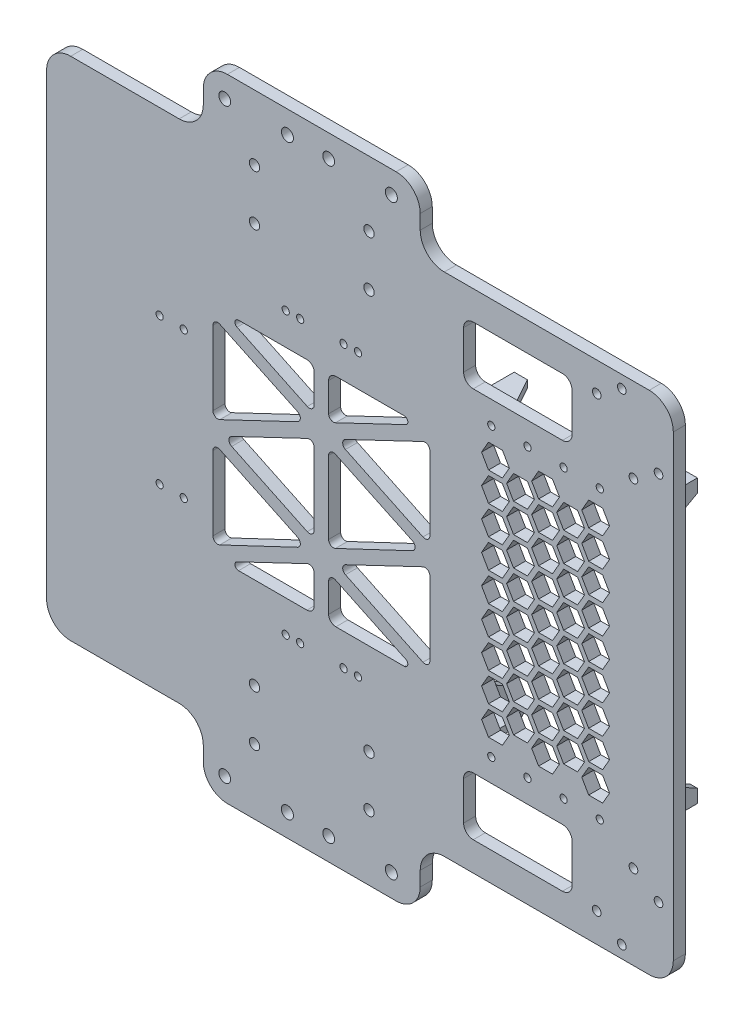
SolidWorks part; units mm, degrees
ref_plane "前视基准面" through (0, 0, 0) normal (0, 0, 1) x (1, 0, 0)
ref_plane "上视基准面" through (0, 0, 0) normal (0, 1, 0) x (1, 0, 0)
ref_plane "右视基准面" through (0, 0, 0) normal (1, 0, 0) x (0, 0, -1)
sketch "草图1" plane through (0, 0, 0) normal (0, 0, 1) x (1, 0, 0)
  line L2 (-130, 95) -> (-130, -95)
  line L3 (-120, -105) -> (-75, -105)
  line L4 (130, 95) -> (130, -95)
  line L5 (126.7518, 102.3765) -> (130, 105) construction
  line L6 (-130, -105) -> (-126.7518, -102.3765) construction
  line L9 (-65, -115) -> (-65, -121)
  line L10 (-55, -131) -> (15, -131)
  line L11 (25, -121) -> (25, -115)
  line L13 (35, -105) -> (120, -105)
  line L14 (126.7518, -102.3765) -> (130, -105) construction
  line L15 (-130, 105) -> (-126.7518, 102.3765) construction
  line L16 (-130, 0) -> (130, 0) construction
  line L17 (35, 105) -> (120, 105)
  line L18 (25, 121) -> (25, 115)
  line L19 (-55, 131) -> (15, 131)
  line L20 (-65, 115) -> (-65, 121)
  line L21 (-120, 105) -> (-75, 105)
  arc A1 (-120, -105) -> (-130, -95) centre (-120, -95) cw
  arc A3 (120, -105) -> (130, -95) centre (120, -95) ccw
  arc A8 (-65, -115) -> (-75, -105) centre (-75, -115) ccw
  arc A9 (25, -115) -> (35, -105) centre (35, -115) cw
  arc A10 (-55, -131) -> (-65, -121) centre (-55, -121) cw
  arc A11 (15, -131) -> (25, -121) centre (15, -121) ccw
  arc A12 (15, 131) -> (25, 121) centre (15, 121) cw
  arc A13 (-55, 131) -> (-65, 121) centre (-55, 121) ccw
  arc A14 (25, 115) -> (35, 105) centre (35, 115) ccw
  arc A15 (-65, 115) -> (-75, 105) centre (-75, 115) cw
  arc A16 (120, 105) -> (130, 95) centre (120, 95) cw
  arc A17 (-120, 105) -> (-130, 95) centre (-120, 95) ccw
  point P0 (0, 0)
  point P40 (25, -105)
  point P45 (25, 105)
  dimension "D2" = 10
  dimension "D3" = 65
  dimension "D4" = 10
  dimension "D5" = 105
  dimension "D7" = 10
  dimension "D8" = 10
  dimension "D10" = 10
  dimension "D12" = 10
  dimension "D13" = 105
  dimension "D18" = 90
  dimension "D19" = 6
extrude "凸台-拉伸1" add sketch "草图1" along normal blind 5
sketch "草图4" plane through (0, 0, 0) normal (0, 0, -1) x (-1, 0, 0)
  line L0 (-39, -47.5) -> (-39, -58.5)
  line L1 (-39, -58.5) -> (-50, -58.5)
  line L2 (-50, -58.5) -> (-50, -55.5)
  line L3 (-50, -55.5) -> (-42, -55.5)
  line L4 (-42, -55.5) -> (-42, -47.5)
  line L5 (-42, -47.5) -> (-39, -47.5)
  line L6 (-130, 0) -> (-25.5592, 0) construction
  line L7 (-130, -95) -> (-130, 95) construction
  line L10 (-130, -95) -> (-130, 95) construction
  dimension "D1" = 11
  dimension "D2" = 11
  dimension "D3" = 3
  dimension "D4" = 3
  dimension "D5" = 80
  dimension "D7" = 55.5
extrude "凸台-拉伸2" add sketch "草图4" along normal blind 20
sketch "草图5" plane through (0, -58.5, 0) normal (0, -1, 0) x (1, 0, 0)
  line L0 (50, -10) -> (44.5, -20)
  line L1 (50, -20) -> (50, 0) construction
  line L2 (50, -20) -> (39, -20) construction
  line L3 (44.5, -20) -> (50, -20)
  line L4 (50, -20) -> (50, -10)
  dimension "D1" = 10
  dimension "D2" = 5.5
extrude "切除-拉伸3" cut sketch "草图5" against normal blind 10
sketch "草图6" plane through (39, 0, 0) normal (-1, 0, 0) x (0, 0, 1)
  line L0 (-20, -53) -> (-10, -47.5)
  line L1 (-20, -58.5) -> (-20, -47.5) construction
  line L2 (-20, -47.5) -> (0, -47.5) construction
  line L3 (-10, -47.5) -> (-20, -47.5)
  line L4 (-20, -47.5) -> (-20, -53)
  dimension "D1" = 10
  dimension "D2" = 5.5
extrude "切除-拉伸4" cut sketch "草图6" against normal blind 10
ref_plane "基准面2" through (77, 0, 0) normal (1, 0, 0) x (0, 0, -1)
mirror "镜向1" about plane through (77, 0, 0) normal (1, 0, 0) of "凸台-拉伸2", "切除-拉伸4", "切除-拉伸3"
mirror "镜向2" about plane through (0, 0, 0) normal (0, 1, 0) of "镜向1"
sketch "草图7" plane through (0, 0, 0) normal (0, 0, -1) x (-1, 0, 0)
  line L4 (-112, -55.5) -> (-104, -55.5) construction
  line L5 (-112, 47.5) -> (-112, 55.5) construction
  line L6 (-112, 55.5) -> (-104, 55.5) construction
  line L7 (-92.013, 36) -> (-94.8997, 41)
  line L8 (-94.8997, 41) -> (-100.6732, 41)
  line L9 (-100.6732, 41) -> (-103.56, 36)
  line L10 (-103.56, 36) -> (-100.6732, 31)
  line L11 (-100.6732, 31) -> (-94.8997, 31)
  line L12 (-94.8997, 31) -> (-92.013, 36)
  line L13 (-77.0019, 36) -> (-97.7865, 36) construction
  line L14 (-74.1151, 31) -> (-71.2284, 36)
  line L15 (-71.2284, 36) -> (-74.1151, 41)
  line L16 (-74.1151, 41) -> (-79.8886, 41)
  line L17 (-79.8886, 41) -> (-82.7754, 36)
  line L18 (-82.7754, 36) -> (-79.8886, 31)
  line L19 (-79.8886, 31) -> (-74.1151, 31)
  line L20 (-92.013, 24) -> (-94.8997, 29)
  line L21 (-93.1677, 30) -> (-90.2809, 25)
  line L22 (-90.2809, 25) -> (-84.5074, 25)
  line L23 (-84.5074, 25) -> (-81.6207, 30)
  line L24 (-81.6207, 30) -> (-84.5074, 35)
  line L25 (-84.5074, 35) -> (-90.2809, 35)
  line L26 (-90.2809, 35) -> (-93.1677, 30)
  line L27 (-84.5074, 37) -> (-81.6207, 42)
  line L28 (-81.6207, 42) -> (-84.5074, 47)
  line L29 (-84.5074, 47) -> (-90.2809, 47)
  line L30 (-90.2809, 47) -> (-93.1677, 42)
  line L31 (-93.1677, 42) -> (-90.2809, 37)
  line L32 (-90.2809, 37) -> (-84.5074, 37)
  line L33 (-79.8886, 43) -> (-74.1151, 43)
  line L34 (-74.1151, 43) -> (-71.2284, 48)
  line L35 (-71.2284, 48) -> (-74.1151, 53)
  line L36 (-74.1151, 53) -> (-79.8886, 53)
  line L37 (-79.8886, 53) -> (-82.7754, 48)
  line L38 (-82.7754, 48) -> (-79.8886, 43)
  line L39 (-94.8997, 43) -> (-92.013, 48)
  line L40 (-92.013, 48) -> (-94.8997, 53)
  line L41 (-94.8997, 53) -> (-100.6732, 53)
  line L42 (-100.6732, 53) -> (-103.56, 48)
  line L43 (-103.56, 48) -> (-100.6732, 43)
  line L44 (-100.6732, 43) -> (-94.8997, 43)
  line L45 (-72.3831, 42) -> (-69.4963, 37)
  line L46 (-69.4963, 37) -> (-63.7228, 37)
  line L47 (-63.7228, 37) -> (-60.8361, 42)
  line L48 (-60.8361, 42) -> (-63.7228, 47)
  line L49 (-63.7228, 47) -> (-69.4963, 47)
  line L50 (-69.4963, 47) -> (-72.3831, 42)
  line L51 (-94.8997, 29) -> (-100.6732, 29)
  line L52 (-100.6732, 29) -> (-103.56, 24)
  line L53 (-103.56, 24) -> (-100.6732, 19)
  line L54 (-100.6732, 19) -> (-94.8997, 19)
  line L55 (-94.8997, 19) -> (-92.013, 24)
  line L56 (-93.1677, 18) -> (-90.2809, 13)
  line L57 (-90.2809, 13) -> (-84.5074, 13)
  line L58 (-84.5074, 13) -> (-81.6207, 18)
  line L59 (-81.6207, 18) -> (-84.5074, 23)
  line L60 (-84.5074, 23) -> (-90.2809, 23)
  line L61 (-90.2809, 23) -> (-93.1677, 18)
  line L62 (-74.1151, 19) -> (-71.2284, 24)
  line L63 (-71.2284, 24) -> (-74.1151, 29)
  line L64 (-74.1151, 29) -> (-79.8886, 29)
  line L65 (-79.8886, 29) -> (-82.7754, 24)
  line L66 (-82.7754, 24) -> (-79.8886, 19)
  line L67 (-79.8886, 19) -> (-74.1151, 19)
  line L68 (-72.3831, 30) -> (-69.4963, 25)
  line L69 (-69.4963, 25) -> (-63.7228, 25)
  line L70 (-63.7228, 25) -> (-60.8361, 30)
  line L71 (-60.8361, 30) -> (-63.7228, 35)
  line L72 (-63.7228, 35) -> (-69.4963, 35)
  line L73 (-69.4963, 35) -> (-72.3831, 30)
  line L74 (-92.013, 12) -> (-94.8997, 17)
  line L75 (-94.8997, 17) -> (-100.6732, 17)
  line L76 (-100.6732, 17) -> (-103.56, 12)
  line L77 (-103.56, 12) -> (-100.6732, 7)
  line L78 (-100.6732, 7) -> (-94.8997, 7)
  line L79 (-94.8997, 7) -> (-92.013, 12)
  line L80 (-93.1677, 6) -> (-90.2809, 1)
  line L81 (-90.2809, 1) -> (-84.5074, 1)
  line L82 (-84.5074, 1) -> (-81.6207, 6)
  line L83 (-81.6207, 6) -> (-84.5074, 11)
  line L84 (-84.5074, 11) -> (-90.2809, 11)
  line L85 (-90.2809, 11) -> (-93.1677, 6)
  line L86 (-74.1151, 7) -> (-71.2284, 12)
  line L87 (-71.2284, 12) -> (-74.1151, 17)
  line L88 (-74.1151, 17) -> (-79.8886, 17)
  line L89 (-79.8886, 17) -> (-82.7754, 12)
  line L90 (-82.7754, 12) -> (-79.8886, 7)
  line L91 (-79.8886, 7) -> (-74.1151, 7)
  line L92 (-72.3831, 18) -> (-69.4963, 13)
  line L93 (-69.4963, 13) -> (-63.7228, 13)
  line L94 (-63.7228, 13) -> (-60.8361, 18)
  line L95 (-60.8361, 18) -> (-63.7228, 23)
  line L96 (-63.7228, 23) -> (-69.4963, 23)
  line L97 (-69.4963, 23) -> (-72.3831, 18)
  line L98 (-92.013, 0) -> (-94.8997, 5)
  line L99 (-94.8997, 5) -> (-100.6732, 5)
  line L100 (-100.6732, 5) -> (-103.56, 0)
  line L101 (-103.56, 0) -> (-100.6732, -5)
  line L102 (-100.6732, -5) -> (-94.8997, -5)
  line L103 (-94.8997, -5) -> (-92.013, 0)
  line L104 (-93.1677, -6) -> (-90.2809, -11)
  line L105 (-90.2809, -11) -> (-84.5074, -11)
  line L106 (-84.5074, -11) -> (-81.6207, -6)
  line L107 (-81.6207, -6) -> (-84.5074, -1)
  line L108 (-84.5074, -1) -> (-90.2809, -1)
  line L109 (-90.2809, -1) -> (-93.1677, -6)
  line L110 (-74.1151, -5) -> (-71.2284, 0)
  line L111 (-71.2284, 0) -> (-74.1151, 5)
  line L112 (-74.1151, 5) -> (-79.8886, 5)
  line L113 (-79.8886, 5) -> (-82.7754, 0)
  line L114 (-82.7754, 0) -> (-79.8886, -5)
  line L115 (-79.8886, -5) -> (-74.1151, -5)
  line L116 (-72.3831, 6) -> (-69.4963, 1)
  line L117 (-69.4963, 1) -> (-63.7228, 1)
  line L118 (-63.7228, 1) -> (-60.8361, 6)
  line L119 (-60.8361, 6) -> (-63.7228, 11)
  line L120 (-63.7228, 11) -> (-69.4963, 11)
  line L121 (-69.4963, 11) -> (-72.3831, 6)
  line L122 (-92.013, -12) -> (-94.8997, -7)
  line L123 (-94.8997, -7) -> (-100.6732, -7)
  line L124 (-100.6732, -7) -> (-103.56, -12)
  line L125 (-103.56, -12) -> (-100.6732, -17)
  line L126 (-100.6732, -17) -> (-94.8997, -17)
  line L127 (-94.8997, -17) -> (-92.013, -12)
  line L128 (-93.1677, -18) -> (-90.2809, -23)
  line L129 (-90.2809, -23) -> (-84.5074, -23)
  line L130 (-84.5074, -23) -> (-81.6207, -18)
  line L131 (-81.6207, -18) -> (-84.5074, -13)
  line L132 (-84.5074, -13) -> (-90.2809, -13)
  line L133 (-90.2809, -13) -> (-93.1677, -18)
  line L134 (-74.1151, -17) -> (-71.2284, -12)
  line L135 (-71.2284, -12) -> (-74.1151, -7)
  line L136 (-74.1151, -7) -> (-79.8886, -7)
  line L137 (-79.8886, -7) -> (-82.7754, -12)
  line L138 (-82.7754, -12) -> (-79.8886, -17)
  line L139 (-79.8886, -17) -> (-74.1151, -17)
  line L140 (-72.3831, -6) -> (-69.4963, -11)
  line L141 (-69.4963, -11) -> (-63.7228, -11)
  line L142 (-63.7228, -11) -> (-60.8361, -6)
  line L143 (-60.8361, -6) -> (-63.7228, -1)
  line L144 (-63.7228, -1) -> (-69.4963, -1)
  line L145 (-69.4963, -1) -> (-72.3831, -6)
  line L146 (-92.013, -24) -> (-94.8997, -19)
  line L147 (-94.8997, -19) -> (-100.6732, -19)
  line L148 (-100.6732, -19) -> (-103.56, -24)
  line L149 (-103.56, -24) -> (-100.6732, -29)
  line L150 (-100.6732, -29) -> (-94.8997, -29)
  line L151 (-94.8997, -29) -> (-92.013, -24)
  line L152 (-93.1677, -30) -> (-90.2809, -35)
  line L153 (-90.2809, -35) -> (-84.5074, -35)
  line L154 (-84.5074, -35) -> (-81.6207, -30)
  line L155 (-81.6207, -30) -> (-84.5074, -25)
  line L156 (-84.5074, -25) -> (-90.2809, -25)
  line L157 (-90.2809, -25) -> (-93.1677, -30)
  line L158 (-74.1151, -29) -> (-71.2284, -24)
  line L159 (-71.2284, -24) -> (-74.1151, -19)
  line L160 (-74.1151, -19) -> (-79.8886, -19)
  line L161 (-79.8886, -19) -> (-82.7754, -24)
  line L162 (-82.7754, -24) -> (-79.8886, -29)
  line L163 (-79.8886, -29) -> (-74.1151, -29)
  line L164 (-72.3831, -18) -> (-69.4963, -23)
  line L165 (-69.4963, -23) -> (-63.7228, -23)
  line L166 (-63.7228, -23) -> (-60.8361, -18)
  line L167 (-60.8361, -18) -> (-63.7228, -13)
  line L168 (-63.7228, -13) -> (-69.4963, -13)
  line L169 (-69.4963, -13) -> (-72.3831, -18)
  line L170 (-92.013, -36) -> (-94.8997, -31)
  line L171 (-94.8997, -31) -> (-100.6732, -31)
  line L172 (-100.6732, -31) -> (-103.56, -36)
  line L173 (-103.56, -36) -> (-100.6732, -41)
  line L174 (-100.6732, -41) -> (-94.8997, -41)
  line L175 (-94.8997, -41) -> (-92.013, -36)
  line L176 (-93.1677, -42) -> (-90.2809, -47)
  line L177 (-90.2809, -47) -> (-84.5074, -47)
  line L178 (-84.5074, -47) -> (-81.6207, -42)
  line L179 (-81.6207, -42) -> (-84.5074, -37)
  line L180 (-84.5074, -37) -> (-90.2809, -37)
  line L181 (-90.2809, -37) -> (-93.1677, -42)
  line L182 (-74.1151, -41) -> (-71.2284, -36)
  line L183 (-71.2284, -36) -> (-74.1151, -31)
  line L184 (-74.1151, -31) -> (-79.8886, -31)
  line L185 (-79.8886, -31) -> (-82.7754, -36)
  line L186 (-82.7754, -36) -> (-79.8886, -41)
  line L187 (-79.8886, -41) -> (-74.1151, -41)
  line L188 (-72.3831, -30) -> (-69.4963, -35)
  line L189 (-69.4963, -35) -> (-63.7228, -35)
  line L190 (-63.7228, -35) -> (-60.8361, -30)
  line L191 (-60.8361, -30) -> (-63.7228, -25)
  line L192 (-63.7228, -25) -> (-69.4963, -25)
  line L193 (-69.4963, -25) -> (-72.3831, -30)
  line L194 (-92.013, -48) -> (-94.8997, -43)
  line L195 (-94.8997, -43) -> (-100.6732, -43)
  line L196 (-100.6732, -43) -> (-103.56, -48)
  line L197 (-103.56, -48) -> (-100.6732, -53)
  line L198 (-100.6732, -53) -> (-94.8997, -53)
  line L199 (-94.8997, -53) -> (-92.013, -48)
  line L206 (-74.1151, -53) -> (-71.2284, -48)
  line L207 (-71.2284, -48) -> (-74.1151, -43)
  line L208 (-74.1151, -43) -> (-79.8886, -43)
  line L209 (-79.8886, -43) -> (-82.7754, -48)
  line L210 (-82.7754, -48) -> (-79.8886, -53)
  line L211 (-79.8886, -53) -> (-74.1151, -53)
  line L212 (-72.3831, -42) -> (-69.4963, -47)
  line L213 (-69.4963, -47) -> (-63.7228, -47)
  line L214 (-63.7228, -47) -> (-60.8361, -42)
  line L215 (-60.8361, -42) -> (-63.7228, -37)
  line L216 (-63.7228, -37) -> (-69.4963, -37)
  line L217 (-69.4963, -37) -> (-72.3831, -42)
  line L218 (-61.9908, 36) -> (-59.104, 31)
  line L219 (-61.9908, 48) -> (-59.104, 43)
  line L220 (-59.104, 43) -> (-53.3305, 43)
  line L221 (-53.3305, 43) -> (-50.4438, 48)
  line L222 (-50.4438, 48) -> (-53.3305, 53)
  line L223 (-53.3305, 53) -> (-59.104, 53)
  line L224 (-59.104, 53) -> (-61.9908, 48)
  line L225 (-59.104, 31) -> (-53.3305, 31)
  line L226 (-53.3305, 31) -> (-50.4438, 36)
  line L227 (-50.4438, 36) -> (-53.3305, 41)
  line L228 (-53.3305, 41) -> (-59.104, 41)
  line L229 (-59.104, 41) -> (-61.9908, 36)
  line L230 (-61.9908, 24) -> (-59.104, 19)
  line L231 (-59.104, 19) -> (-53.3305, 19)
  line L232 (-53.3305, 19) -> (-50.4438, 24)
  line L233 (-50.4438, 24) -> (-53.3305, 29)
  line L234 (-53.3305, 29) -> (-59.104, 29)
  line L235 (-59.104, 29) -> (-61.9908, 24)
  line L236 (-61.9908, 12) -> (-59.104, 7)
  line L237 (-59.104, 7) -> (-53.3305, 7)
  line L238 (-53.3305, 7) -> (-50.4438, 12)
  line L239 (-50.4438, 12) -> (-53.3305, 17)
  line L240 (-53.3305, 17) -> (-59.104, 17)
  line L241 (-59.104, 17) -> (-61.9908, 12)
  line L242 (-61.9908, 0) -> (-59.104, -5)
  line L243 (-59.104, -5) -> (-53.3305, -5)
  line L244 (-53.3305, -5) -> (-50.4438, 0)
  line L245 (-50.4438, 0) -> (-53.3305, 5)
  line L246 (-53.3305, 5) -> (-59.104, 5)
  line L247 (-59.104, 5) -> (-61.9908, 0)
  line L248 (-61.9908, -12) -> (-59.104, -17)
  line L249 (-59.104, -17) -> (-53.3305, -17)
  line L250 (-53.3305, -17) -> (-50.4438, -12)
  line L251 (-50.4438, -12) -> (-53.3305, -7)
  line L252 (-53.3305, -7) -> (-59.104, -7)
  line L253 (-59.104, -7) -> (-61.9908, -12)
  line L254 (-61.9908, -24) -> (-59.104, -29)
  line L255 (-59.104, -29) -> (-53.3305, -29)
  line L256 (-53.3305, -29) -> (-50.4438, -24)
  line L257 (-50.4438, -24) -> (-53.3305, -19)
  line L258 (-53.3305, -19) -> (-59.104, -19)
  line L259 (-59.104, -19) -> (-61.9908, -24)
  line L260 (-61.9908, -36) -> (-59.104, -41)
  line L261 (-59.104, -41) -> (-53.3305, -41)
  line L262 (-53.3305, -41) -> (-50.4438, -36)
  line L263 (-50.4438, -36) -> (-53.3305, -31)
  line L264 (-53.3305, -31) -> (-59.104, -31)
  line L265 (-59.104, -31) -> (-61.9908, -36)
  line L266 (-61.9908, -48) -> (-59.104, -53)
  line L267 (-59.104, -53) -> (-53.3305, -53)
  line L268 (-53.3305, -53) -> (-50.4438, -48)
  line L269 (-50.4438, -48) -> (-53.3305, -43)
  line L270 (-53.3305, -43) -> (-59.104, -43)
  line L271 (-59.104, -43) -> (-61.9908, -48)
  line L272 (-93.1677, -54) -> (-90.2809, -59) [skipped]
  line L273 (-90.2809, -59) -> (-84.5074, -59) [skipped]
  line L274 (-84.5074, -59) -> (-81.6207, -54) [skipped]
  line L275 (-81.6207, -54) -> (-84.5074, -49) [skipped]
  line L276 (-84.5074, -49) -> (-90.2809, -49) [skipped]
  line L277 (-90.2809, -49) -> (-93.1677, -54) [skipped]
  circle A0 centre (-97.7865, 36) radius 5 construction
  circle A1 centre (-77.0019, 36) radius 5 construction
  circle A2 centre (-87.3942, 30) radius 5 construction
  circle A3 centre (-87.3942, 42) radius 5 construction
  circle A4 centre (-77.0019, 48) radius 5 construction
  circle A5 centre (-97.7865, 48) radius 5 construction
  circle A6 centre (-66.6096, 42) radius 5 construction
  circle A7 centre (-56.2173, 48) radius 5 construction
  point P4 (-87.3942, 37)
  dimension "D1" = 2
  dimension "D3" = 10
  dimension "D4" = 10
  dimension "D5" = 2
  dimension "D7" = 10
  dimension "D11" = 10
  dimension "D14" = 10
  dimension "D15" = 10
  dimension "D20" = 10
  dimension "D2" = 2
  dimension "D6" = 2
  dimension "D8" = 2
  dimension "D9" = 2
  dimension "D10" = 2
  dimension "D12" = 2
  dimension "D13" = 2
  dimension "D16" = 2
  dimension "D17" = 2
  dimension "D19" = 2
  dimension "D21" = 9
  dimension "D22" = 2.5
  dimension "D23" = 2.5
  dimension "D24" = 8.44
  dimension "D18" = 8
extrude "切除-拉伸5" cut sketch "草图7" against normal blind 5
sketch "草图8" plane through (0, 0, 0) normal (0, 0, -1) x (-1, 0, 0)
  line L0 (-75.3677, 120) -> (-75.3677, -120)
  line L1 (-100.0285, 77.2863) -> (-100.0285, -77.2863)
  line L2 (-100.0285, 77.2863) -> (-75.3677, 120)
  line L3 (-100.0285, -77.2863) -> (-75.3677, -120)
  line L4 (-37.1297, 0) -> (-146.8562, 0) construction
  dimension "D1" = 30
  dimension "D2" = 30
  dimension "D3" = 120
  dimension "D4" = 120
sketch "草图9" plane through (0, 0, 0) normal (0, 0, -1) x (-1, 0, 0)
  line L0 (148.8518, 0) -> (-37.1297, 0) construction
  line L1 (-29, 41) -> (-29, 4)
  line L2 (-25, -45) -> (13, -45)
  line L3 (61, -41) -> (61, -4)
  line L4 (57, 45) -> (19, 45)
  line L14 (-29, 41) -> (9.8049, 22.5)
  line L15 (57, 0) -> (19, -18.1163)
  line L16 (130, 95) -> (130, -95) construction
  line L17 (63, 93) -> (118, 93)
  line L18 (63, 93) -> (63, 66)
  line L19 (63, 66) -> (118, 66)
  line L20 (118, 93) -> (118, 66)
  line L21 (75, 105) -> (120, 105) construction
  line L22 (63, -66) -> (118, -66)
  line L23 (118, -93) -> (118, -66)
  line L24 (63, -93) -> (118, -93)
  line L25 (63, -93) -> (63, -66)
  line L26 (-120, 105) -> (-35, 105) construction
  line L27 (-43, 93) -> (-88, 93)
  line L28 (-43, 93) -> (-43, 69)
  line L29 (-43, 69) -> (-88, 69)
  line L30 (-88, 93) -> (-88, 69)
  line L31 (-130, -95) -> (-130, 95) construction
  line L32 (-43, -69) -> (-88, -69)
  line L33 (-88, -93) -> (-88, -69)
  line L34 (-43, -93) -> (-88, -93)
  line L35 (-43, -93) -> (-43, -69)
  line L36 (-25, 45) -> (13, 26.8837)
  line L37 (-25, -45) -> (13, -26.8837)
  line L38 (61, 41) -> (22.0746, 22.5575)
  line L39 (-25.5359, 0) -> (13, -18.258)
  line L40 (57, 45) -> (19, 26.8837)
  line L41 (57, -45) -> (19, -26.8837)
  line L42 (16, 61.4977) -> (16, -60.5731) construction
  line L43 (13, 45) -> (13, 26.8837)
  line L44 (19, 45) -> (19, 26.8837)
  line L45 (13, 18.258) -> (13, -18.258)
  line L46 (9.8049, 22.5) -> (-29, 4)
  line L47 (19, 18.1163) -> (57, 0)
  line L48 (22.0746, 22.5575) -> (61, 4)
  line L49 (13, 18.258) -> (-25.5359, 0)
  line L50 (19, 18.1163) -> (19, -18.1163)
  line L51 (22.0746, -22.5575) -> (61, -41)
  line L52 (9.8049, -22.5) -> (-29, -41)
  line L53 (9.8049, -22.5) -> (-29, -4)
  line L54 (22.0746, -22.5575) -> (61, -4)
  line L55 (13, -26.8837) -> (13, -45)
  line L56 (19, -26.8837) -> (19, -45)
  line L57 (13, 45) -> (-25, 45)
  line L58 (-29, -4) -> (-29, -41)
  line L59 (19, -45) -> (57, -45)
  line L60 (61, 4) -> (61, 41)
  line L61 (-44, 41) -> (-44, -37.8122) construction
  dimension "D1" = 45
  dimension "D2" = 45
  dimension "D3" = 15
  dimension "D4" = 90
  dimension "D5" = 1
  dimension "D7" = 12
  dimension "D8" = 12
  dimension "D9" = 27
  dimension "D10" = 55
  dimension "D11" = 12
  dimension "D12" = 45
  dimension "D13" = 42
  dimension "D14" = 24
  dimension "D21" = 4
  dimension "D22" = 4
  dimension "D23" = 4
  dimension "D24" = 4
  dimension "D26" = 4
  dimension "D27" = 3
  dimension "D28" = 45
extrude "切除-拉伸6" cut sketch "草图9" against normal blind 5 contours L27 L30 L29 L28 | L34 L35 L32 L33 | L4 L44 L40 | L48 L60 L38 | L47 L50 L15 | L54 L51 L3 | L56 L59 L41 | L55 L37 L2 | L53 L58 L52 | L45 L49 L39 | L46 L14 L1 | L43 L57 L36 | L57 L36 L43 region at (16.065, 22.5, 0) region at (-0.3333, -38.9612, 0) region at (-48.0249, -22.5192, 0) region at (-31.6667, 38.9612, 0) region at (-31.6667, 0, 0) region at (65.5, 81, 0) region at (65.5, -81, 0) region at (-0.3333, 38.9612, 0) region at (-48.0249, 22.5192, 0) region at (-0.1547, 0, 0) region at (-31.6667, -38.9612, 0) region at (16.065, -22.5, 0)
fillet "圆角1" radius 4 8 edges at (43, -93, 2.5) (88, -69, 2.5) (43, -69, 2.5) (88, -93, 2.5) (88, 69, 2.5) (43, 69, 2.5) (43, 93, 2.5) (88, 93, 2.5)
fillet "圆角2" radius 1.5 4 edges at (25, -45, 2.5) (-57, -45, 2.5) (25, 45, 2.5) (-57, 45, 2.5)
fillet "圆角3" radius 2 22 edges at (29, -4, 2.5) (29, 4, 2.5) (-13, -18.258, 2.5) (-61, -41, 2.5) (-61, 4, 2.5) (-13, -26.8837, 2.5) (-13, 18.258, 2.5) (-61, -4, 2.5) (-22.0746, -22.5575, 2.5) (25.5359, 0, 2.5) (-22.0746, 22.5575, 2.5) (-61, 41, 2.5) (-19, 26.8837, 2.5) (-19, -26.8837, 2.5) (-19, -18.1163, 2.5) (29, -41, 2.5) (29, 41, 2.5) (-57, 0, 2.5) (-9.8049, -22.5, 2.5) (-13, 26.8837, 2.5) (-9.8049, 22.5, 2.5) (-19, 18.1163, 2.5)
fillet "圆角4" radius 3 4 edges at (-13, -45, 2.5) (-13, 45, 2.5) (-19, -45, 2.5) (-19, 45, 2.5)
sketch "草图10" plane through (0, 0, 0) normal (0, 0, -1) x (-1, 0, 0)
  line L0 (-37.1297, 0) -> (-146.8562, 0) construction
  line L1 (-37.1297, 0) -> (-146.8562, 0) construction
  circle A0 centre (-123.8743, 76.9597) radius 1.8 construction
  circle A1 centre (-113.4687, 70.0334) radius 1.8 construction
  circle A2 centre (-108.6364, 99.852) radius 1.8 construction
  circle A3 centre (-98.2308, 92.9256) radius 1.8 construction
  circle A11 centre (-13.0267, 121.679) radius 2.5 construction
  circle A12 centre (56.0941, 121.679) radius 2.45 construction
  circle A13 centre (30.0941, 121.679) radius 2.5 construction
  circle A14 centre (12.9733, 121.679) radius 2.45 construction
  circle A15 centre (-123.8743, 76.9597) radius 1.8
  circle A16 centre (-113.4687, 70.0334) radius 1.8
  circle A17 centre (-108.6364, 99.852) radius 1.8
  circle A18 centre (-98.2308, 92.9256) radius 1.8
  circle A26 centre (-13.0267, 121.679) radius 2.5
  circle A27 centre (56.0941, 121.679) radius 2.45
  circle A28 centre (30.0941, 121.679) radius 2.5
  circle A29 centre (12.9733, 121.679) radius 2.45
  circle A30 centre (12.9733, -121.679) radius 2.45
  circle A31 centre (30.0941, -121.679) radius 2.5
  circle A32 centre (56.0941, -121.679) radius 2.45
  circle A33 centre (-13.0267, -121.679) radius 2.5
  circle A41 centre (-98.2308, -92.9256) radius 1.8
  circle A42 centre (-108.6364, -99.852) radius 1.8
  circle A43 centre (-113.4687, -70.0334) radius 1.8
  circle A44 centre (-123.8743, -76.9597) radius 1.8
  circle A45 centre (-99.5, 59.5) radius 1.5 construction
  circle A46 centre (-84.5, 59.5) radius 1.5 construction
  circle A47 centre (-69.5, 59.5) radius 1.5 construction
  circle A48 centre (-54.5, 59.5) radius 1.5 construction
  circle A49 centre (0.8061, 58.25) radius 1.5 construction
  circle A50 centre (6.8061, 58.25) radius 1.5 construction
  circle A51 centre (24.8061, 58.25) radius 1.5 construction
  circle A52 centre (30.8061, 58.25) radius 1.5 construction
  circle A53 centre (-99.5, 59.5) radius 1.5
  circle A54 centre (-84.5, 59.5) radius 1.5
  circle A55 centre (-69.5, 59.5) radius 1.5
  circle A56 centre (-54.5, 59.5) radius 1.5
  circle A57 centre (0.8061, 58.25) radius 1.5
  circle A58 centre (6.8061, 58.25) radius 1.5
  circle A59 centre (24.8061, 58.25) radius 1.5
  circle A60 centre (30.8061, 58.25) radius 1.5
  circle A61 centre (30.8061, -58.25) radius 1.5
  circle A62 centre (24.8061, -58.25) radius 1.5
  circle A63 centre (6.8061, -58.25) radius 1.5
  circle A64 centre (0.8061, -58.25) radius 1.5
  circle A65 centre (-54.5, -59.5) radius 1.5
  circle A66 centre (-69.5, -59.5) radius 1.5
  circle A67 centre (-84.5, -59.5) radius 1.5
  circle A68 centre (-99.5, -59.5) radius 1.5
  circle A89 centre (73.1015, 30.3) radius 1.5 construction
  circle A90 centre (83.1015, 30.3) radius 1.5 construction
  circle A91 centre (73.1015, 30.3) radius 1.5
  circle A92 centre (83.1015, 30.3) radius 1.5
  circle A93 centre (83.1015, -30.3) radius 1.5
  circle A94 centre (73.1015, -30.3) radius 1.5
  circle A95 centre (43.75, 83) radius 2.15 construction
  circle A96 centre (43.75, 104) radius 2.15 construction
  circle A97 centre (-3.75, 83) radius 2.15 construction
  circle A98 centre (-3.75, 104) radius 2.15 construction
  circle A99 centre (43.75, 83) radius 2.15
  circle A100 centre (43.75, 104) radius 2.15
  circle A101 centre (-3.75, 83) radius 2.15
  circle A102 centre (-3.75, 104) radius 2.15
  circle A103 centre (-3.75, -104) radius 2.15
  circle A104 centre (-3.75, -83) radius 2.15
  circle A105 centre (43.75, -104) radius 2.15
  circle A106 centre (43.75, -83) radius 2.15
extrude "切除-拉伸7" cut sketch "草图10" against normal through all
equation "\"45、\"=43.7672"
